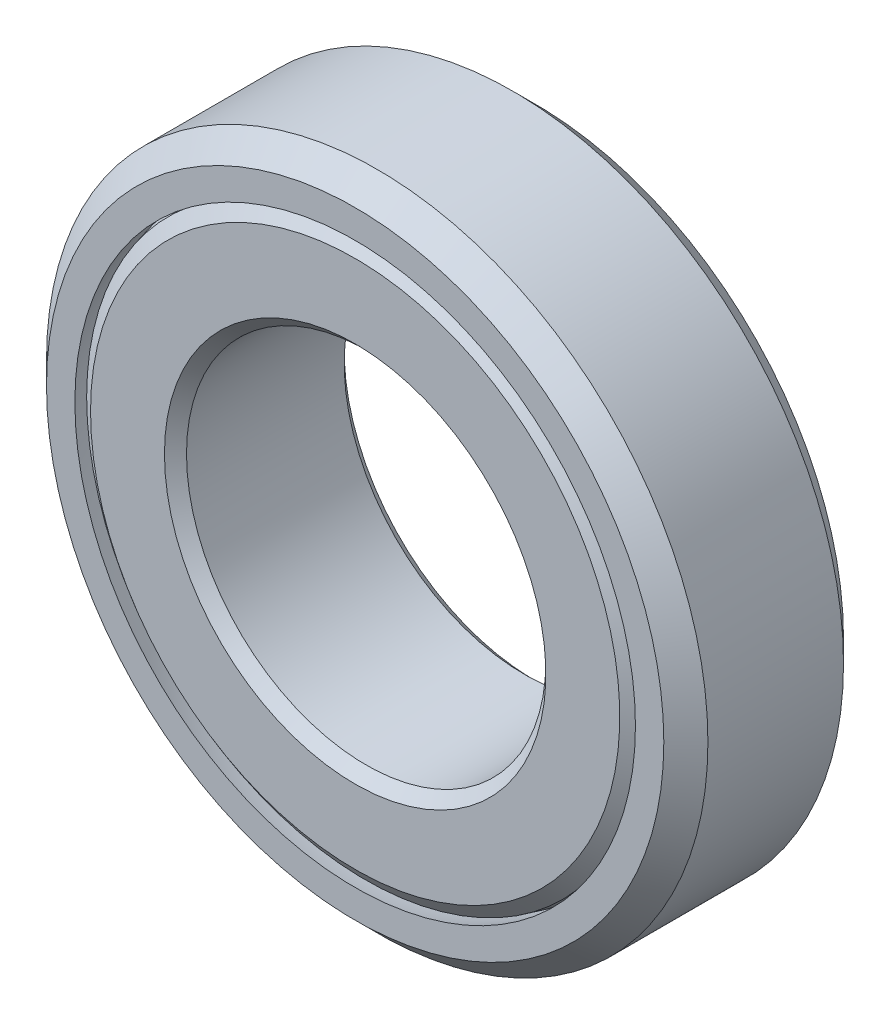
SolidWorks part; units mm, degrees
material "Onyx (Density Only)"
ref_plane "Front Plane" through (0, 0, 0) normal (0, 0, 1) x (1, 0, 0)
ref_plane "Top Plane" through (0, 0, 0) normal (0, 1, 0) x (1, 0, 0)
ref_plane "Right Plane" through (0, 0, 0) normal (1, 0, 0) x (0, 0, -1)
sketch "Sketch1" plane through (0, 0, 0) normal (0, 0, 1) x (1, 0, 0)
  circle A0 centre (0, 0) radius 8.15
  dimension "D1" = 16.3
sketch "Sketch2" plane through (0, 0, 0) normal (0, 1, 0) x (1, 0, 0)
  line L0 (-8.15, 0) -> (8.15, 0) construction
  line L1 (-8.15, 0) -> (8.15, 0)
  line L3 (-8.15, -4.075) -> (8.15, -4.075)
  line L4 (-8.15, -4.075) -> (-8.15, 4.075)
  line L5 (-8.15, 4.075) -> (8.15, 4.075)
  line L6 (8.15, -4.075) -> (8.15, 4.075)
  line L7 (-8.15, -4.075) -> (8.15, 4.075) construction
  line L8 (-8.15, 4.075) -> (8.15, -4.075) construction
  circle A0 centre (0, 0) radius 8.15
  circle A1 centre (0, 0) radius 13.15
  dimension "D1" = 8.15
  dimension "D2" = 5
sketch "Sketch4" plane through (0, 0, 0) normal (0, 1, 0) x (1, 0, 0)
  line L1 (-8.15, 0) -> (8.15, 0) construction
  line L2 (-8.15, 0) -> (8.15, 0)
  line L3 (0, -13.15) -> (0, 13.15)
  line L13 (-8.15, -4.075) -> (8.15, -4.075)
  line L14 (8.15, -4.075) -> (8.15, 4.075)
  line L15 (8.15, 4.075) -> (-8.15, 4.075)
  line L16 (-8.15, 4.075) -> (-8.15, -4.075)
  line L17 (-12.5027, -4.075) -> (12.5027, -4.075)
  line L18 (8.15, -4.075) -> (8.15, 4.075)
  line L19 (12.5027, 4.075) -> (-12.5027, 4.075)
  line L20 (-8.15, 4.075) -> (-8.15, -4.075)
  circle A1 centre (0, 0) radius 13.15
  circle A3 centre (0, 0) radius 13.15
  circle A5 centre (0, 0) radius 8.15
  circle A6 centre (0, 0) radius 8.15
  dimension "D1" = 0
  dimension "D2" = 0
  dimension "D3" = 0
revolve "Revolve4" add sketch "Sketch4" angle 360 about L3
sketch "Sketch6" plane through (0, 0, 0) normal (0, 1, 0) x (1, 0, 0)
  line L1 (-8.15, 4.075) -> (-8.15, -4.075) construction
  line L2 (12.5027, 4.075) -> (-12.5027, 4.075) construction
  line L3 (8.15, -4.075) -> (8.15, 4.075) construction
  line L12 (-12.5027, -4.075) -> (12.5027, -4.075) construction
  line L13 (0, -13.15) -> (0, 13.15) construction
  line L14 (-8.15, 0) -> (8.15, 0) construction
  line L15 (-8.15, 4.075) -> (-8.15, -4.075)
  line L16 (15.6274, 4.075) -> (-15.6274, 4.075)
  line L17 (8.15, -4.075) -> (8.15, 4.075)
  line L18 (-15.6274, -4.075) -> (15.6274, -4.075)
  line L19 (0, -13.15) -> (0, 13.15)
  line L20 (-8.15, 0) -> (8.15, 0)
  circle A0 centre (0, 0) radius 16.15
  circle A1 centre (0, 0) radius 8.15
  circle A3 centre (0, 0) radius 8.15
  circle A5 centre (0, 0) radius 13.15
  circle A6 centre (0, 0) radius 13.15
  circle A7 centre (0, 0) radius 13.35
  dimension "D1" = 0
  dimension "D2" = 0
  dimension "D3" = 3
  dimension "D4" = 0.2
revolve "Revolve5" add sketch "Sketch6" angle 360 about L19
sketch "Sketch7" plane through (0, 0, 0) normal (0, 0, 1) x (1, 0, 0)
  circle A0 centre (0, 0) radius 18.6274
  circle A1 centre (0, 0) radius 15.6274
  circle A2 centre (0, 0) radius 15.6274
  dimension "D1" = 0
  dimension "D2" = 3
extrude "Cut-Extrude1" cut sketch "Sketch7" against normal through all both and the other way through all
sketch "Sketch9" plane through (0, 0, 0) normal (0, 0, 1) x (1, 0, 0)
  circle A0 centre (0, 0) radius 15
  circle A1 centre (0, 0) radius 15.6274
  circle A2 centre (0, 0) radius 15.6274
  dimension "D2" = 30
  dimension "D1" = 0
extrude "Cut-Extrude2" cut sketch "Sketch9" against normal through all both and the other way through all
chamfer "Chamfer1" distance 1 2 edges at (15, 0, -4.075) (15, 0, 4.075)
chamfer "Chamfer3" distance 0.5 4 edges at (12.5027, 0, -4.075) (12.5027, 0, 4.075) (8.15, 0, -4.075) (8.15, 0, 4.075)
